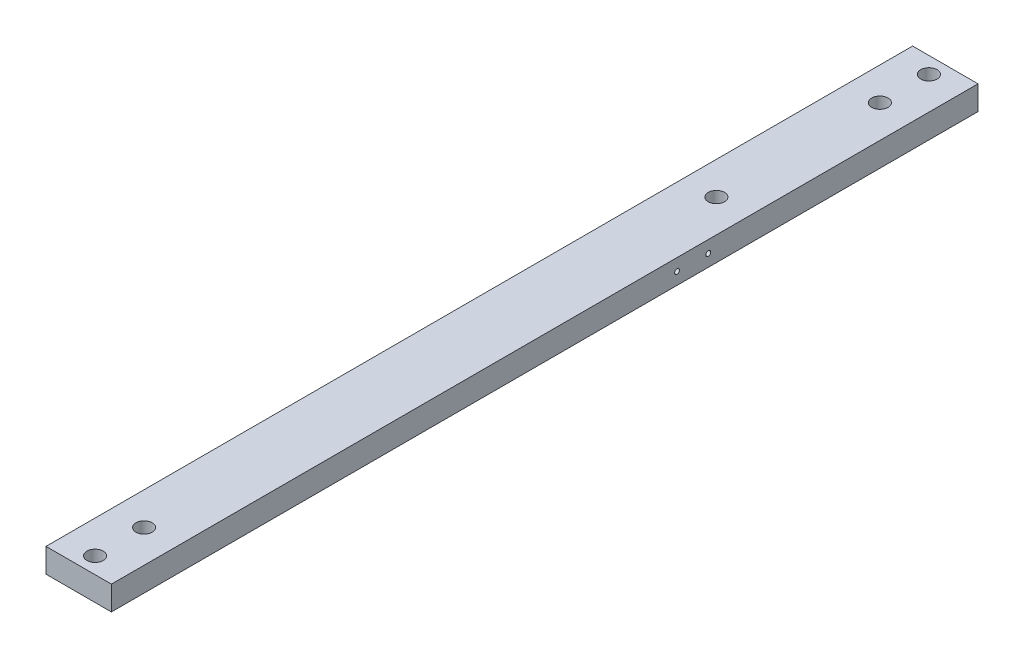
SolidWorks part; units mm, degrees
ref_plane "前视基准面" through (0, 0, 0) normal (0, 0, 1) x (1, 0, 0)
ref_plane "上视基准面" through (0, 0, 0) normal (0, 1, 0) x (1, 0, 0)
ref_plane "右视基准面" through (0, 0, 0) normal (1, 0, 0) x (0, 0, -1)
other "Configuration Table"
sketch "草图1" plane through (0, 0, 0) normal (0, 1, 0) x (1, 0, 0)
  line L1 (0, 0) -> (8, 0)
  line L2 (0, 0) -> (0, -106)
  line L3 (0, -106) -> (8, -106)
  line L4 (8, 0) -> (8, -106)
  dimension "D1" = 106
  dimension "D2" = 8
extrude "凸台-拉伸1" add sketch "草图1" along normal blind 2.95
sketch "草图2" plane through (0, 2.95, 0) normal (0, 1, 0) x (1, 0, 0)
  line L0 (0, -2) -> (8, -2)
  line L1 (0, 0) -> (0, -106) construction
  line L2 (8, -106) -> (8, 0) construction
  line L3 (8, 0) -> (0, 0) construction
  line L4 (0, -106) -> (8, -106) construction
  circle A0 centre (4, -8) radius 0.7
  circle A1 centre (4, -8) radius 1
  circle A2 centre (4, -2) radius 0.7
  circle A3 centre (4, -2) radius 1
  circle A4 centre (4, -104) radius 0.7
  circle A5 centre (4, -104) radius 1
  circle A6 centre (4, -98) radius 0.7
  circle A7 centre (4, -98) radius 1
  circle A8 centre (4, -28) radius 1
  circle A9 centre (4, -28) radius 0.7
  dimension "D1" = 2
  dimension "D2" = 1.4
  dimension "D3" = 2
  dimension "D4" = 1.4
  dimension "D7" = 2
  dimension "D8" = 1.4
  dimension "D9" = 2
  dimension "D10" = 1.4
  dimension "D5" = 2
  dimension "D6" = 6
  dimension "D11" = 2
  dimension "D12" = 6
  dimension "D13" = 20
extrude "切除-拉伸1" cut sketch "草图2" against normal through all contours A2 | A0 | A6 | A4 | A9
extrude "切除-拉伸2" cut sketch "草图2<3>" against normal blind 1.5 contours A1 | A3 | A5 | A7 | A8
sketch "草图2<3>" plane through (0, 2.95, 0) normal (0, 1, 0) x (1, 0, 0) same geometry as "草图2"
sketch "草图3" plane through (8, 0, 0) normal (1, 0, 0) x (0, 0, -1)
  circle A0 centre (-33, 1.475) radius 0.3
  circle A1 centre (-36.8, 1.475) radius 0.3
  point P2 (0, 0)
  dimension "D1" = 0.6
  dimension "D2" = 3.8
  dimension "D3" = 1.475
  dimension "D4" = 33
extrude "切除-拉伸3" cut sketch "草图3" against normal through all contours A0 | A1
